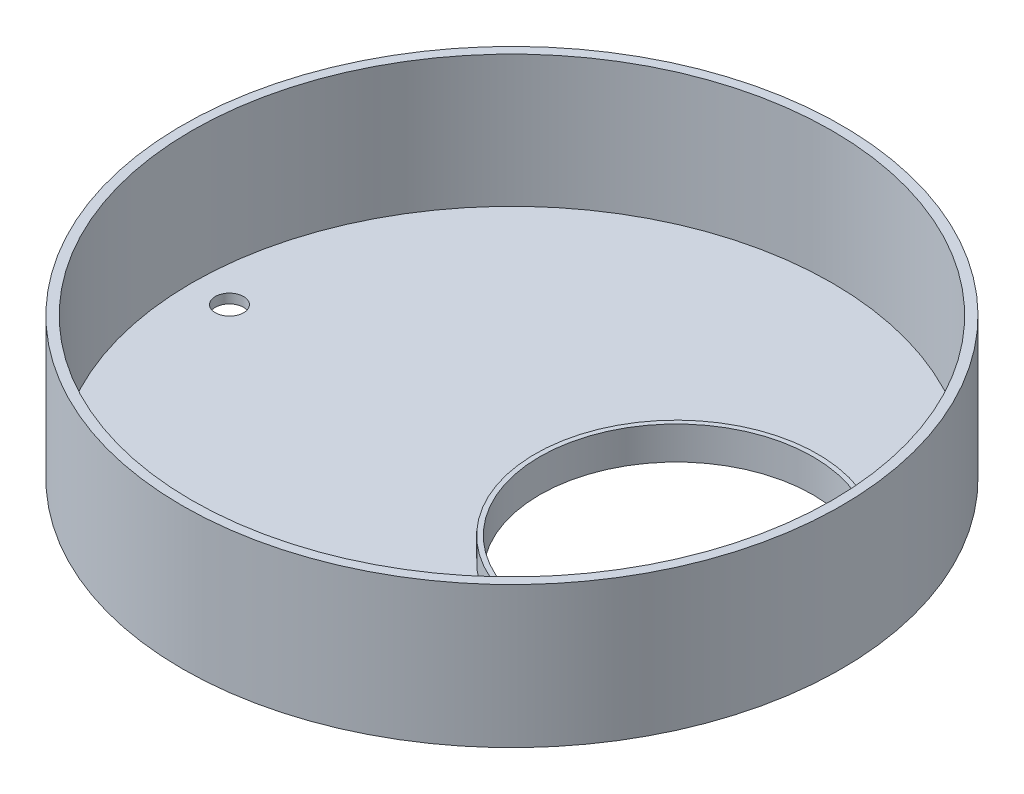
SolidWorks part; units mm, degrees
ref_plane "Front Plane" through (0, 0, 0) normal (0, 0, 1) x (1, 0, 0)
ref_plane "Top Plane" through (0, 0, 0) normal (0, 1, 0) x (1, 0, 0)
ref_plane "Right Plane" through (0, 0, 0) normal (1, 0, 0) x (0, 0, -1)
sketch "Sketch1" plane through (0, 0, 0) normal (0, 1, 0) x (1, 0, 0)
  circle A0 centre (0, 0) radius 70
  dimension "D1" = 140
extrude "Boss-Extrude1" add sketch "Sketch1" along normal blind 30
shell "Shell1" thickness 2 removed face at (0, 30, 70)
sketch "Sketch2" plane through (0, 2, 0) normal (0, 1, 0) x (1, 0, 0)
  line L0 (0, 0) -> (68, 0) construction
  circle A0 centre (34.9213, 0) radius 29
  dimension "D1" = 58
extrude "Extrude-Thin1" add sketch "Sketch2" along normal blind 5 thin thin type one direction wall 4
sketch "Sketch3" plane through (0, 7, 0) normal (0, 1, 0) x (1, 0, 0)
  circle A1 centre (34.9213, 0) radius 33
  circle A3 centre (34.9213, 0) radius 30
  dimension "D1" = 66
  dimension "D2" = 60
extrude "Cut-Extrude1" cut sketch "Sketch3" against normal blind 5
sketch "Sketch4" plane through (0, 2, 0) normal (0, 1, 0) x (1, 0, 0)
  circle A0 centre (34.9213, 0) radius 29
  circle A1 centre (34.9213, 0) radius 30 construction
extrude "Cut-Extrude2" cut sketch "Sketch4" against normal blind 2
sketch "Sketch5" plane through (0, 2, 0) normal (0, 1, 0) x (1, 0, 0)
  circle A0 centre (-60, 0) radius 3
  dimension "D1" = 6
  dimension "D2" = 60
extrude "Cut-Extrude3" cut sketch "Sketch5" against normal mid plane 10
